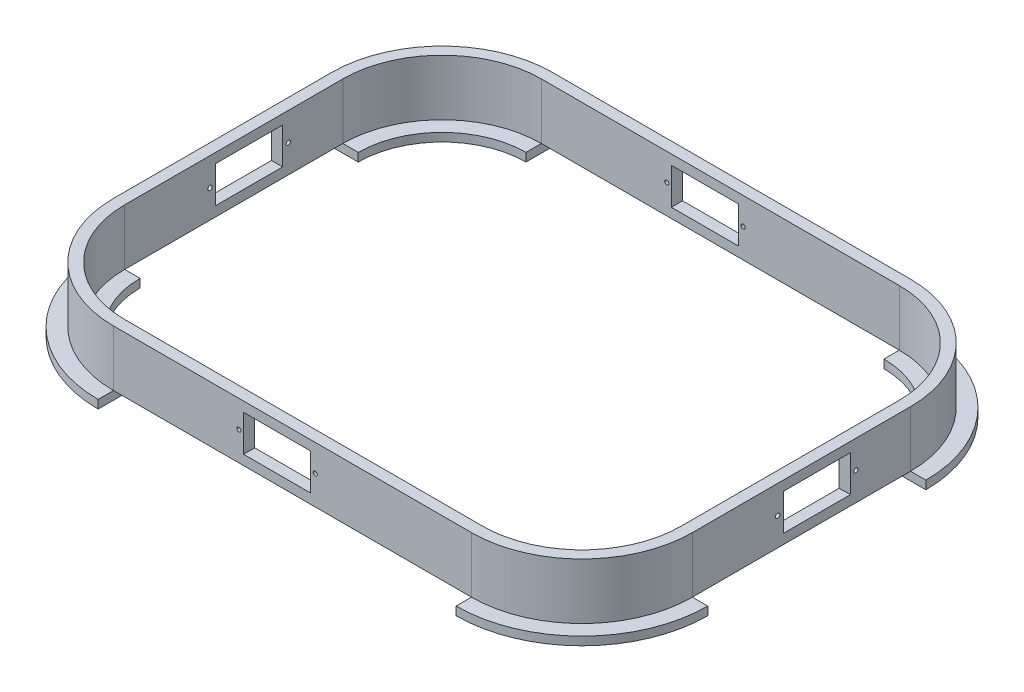
SolidWorks part; units mm, degrees
material "PVC Rigid"
ref_plane "Front Plane" through (0, 0, 0) normal (0, 0, 1) x (1, 0, 0)
ref_plane "Top Plane" through (0, 0, 0) normal (0, 1, 0) x (1, 0, 0)
ref_plane "Right Plane" through (0, 0, 0) normal (1, 0, 0) x (0, 0, -1)
sketch "Sketch1" plane through (0, 0, 0) normal (0, 1, 0) x (1, 0, 0)
  line L0 (-64, 84) -> (64, 84)
  line L1 (-64, -69) -> (64, -69)
  line L2 (-94, -39) -> (-94, 39)
  line L3 (-64, 69) -> (64, 69)
  line L4 (94, -39) -> (94, 39)
  line L5 (-94, -69) -> (94, 69) construction
  line L6 (-94, 69) -> (94, -69) construction
  line L7 (109, -39) -> (109, 39)
  line L8 (-64, -84) -> (64, -84)
  line L9 (-109, -39) -> (-109, 39)
  line L10 (-64, 76.5) -> (64, 76.5) construction
  line L11 (101.5, -39) -> (101.5, 39) construction
  line L12 (-64, -76.5) -> (64, -76.5) construction
  line L13 (-101.5, -39) -> (-101.5, 39) construction
  line L14 (-64, 74.5) -> (64, 74.5)
  line L15 (99.5, -39) -> (99.5, 39)
  line L16 (-64, -74.5) -> (64, -74.5)
  line L17 (-99.5, -39) -> (-99.5, 39)
  line L18 (-64, 78.5) -> (64, 78.5)
  line L19 (103.5, -39) -> (103.5, 39)
  line L20 (-64, -78.5) -> (64, -78.5)
  line L21 (-103.5, -39) -> (-103.5, 39)
  line L22 (-64, 80.5) -> (64, 80.5)
  line L23 (105.5, -39) -> (105.5, 39)
  line L24 (-64, -80.5) -> (64, -80.5)
  line L25 (-105.5, -39) -> (-105.5, 39)
  line L26 (-64, 72.5) -> (64, 72.5)
  line L27 (97.5, -39) -> (97.5, 39)
  line L28 (-64, -72.5) -> (64, -72.5)
  line L29 (-97.5, -39) -> (-97.5, 39)
  line L31 (-64, -189.9551) -> (64, -189.9551)
  line L32 (-64, -189.9551) -> (-64, 189.9551)
  line L33 (-64, 189.9551) -> (64, 189.9551)
  line L34 (64, -189.9551) -> (64, 189.9551)
  line L35 (-64, -189.9551) -> (64, 189.9551) construction
  line L36 (-64, 189.9551) -> (64, -189.9551) construction
  line L37 (-310.5434, -39) -> (310.5434, -39)
  line L38 (-310.5434, -39) -> (-310.5434, 39)
  line L39 (-310.5434, 39) -> (310.5434, 39)
  line L40 (310.5434, -39) -> (310.5434, 39)
  line L41 (-310.5434, -39) -> (310.5434, 39) construction
  line L42 (-310.5434, 39) -> (310.5434, -39) construction
  arc A0 (64, -69) -> (94, -39) centre (64, -39) ccw
  arc A1 (-64, -69) -> (-94, -39) centre (-64, -39) cw
  arc A2 (64, 69) -> (94, 39) centre (64, 39) cw
  arc A3 (-94, 39) -> (-64, 69) centre (-64, 39) cw
  arc A4 (64, 84) -> (109, 39) centre (64, 39) cw
  arc A5 (64, -84) -> (109, -39) centre (64, -39) ccw
  arc A6 (-64, -84) -> (-109, -39) centre (-64, -39) cw
  arc A7 (-109, 39) -> (-64, 84) centre (-64, 39) cw
  arc A8 (64, 76.5) -> (101.5, 39) centre (64, 39) cw construction
  arc A9 (64, -76.5) -> (101.5, -39) centre (64, -39) ccw construction
  arc A10 (-64, -76.5) -> (-101.5, -39) centre (-64, -39) cw construction
  arc A11 (-101.5, 39) -> (-64, 76.5) centre (-64, 39) cw construction
  arc A12 (64, 74.5) -> (99.5, 39) centre (64, 39) cw
  arc A13 (64, -74.5) -> (99.5, -39) centre (64, -39) ccw
  arc A14 (-64, -74.5) -> (-99.5, -39) centre (-64, -39) cw
  arc A15 (-99.5, 39) -> (-64, 74.5) centre (-64, 39) cw
  arc A16 (64, 78.5) -> (103.5, 39) centre (64, 39) cw
  arc A17 (64, -78.5) -> (103.5, -39) centre (64, -39) ccw
  arc A18 (-64, -78.5) -> (-103.5, -39) centre (-64, -39) cw
  arc A19 (-103.5, 39) -> (-64, 78.5) centre (-64, 39) cw
  arc A20 (64, 80.5) -> (105.5, 39) centre (64, 39) cw
  arc A21 (64, -80.5) -> (105.5, -39) centre (64, -39) ccw
  arc A22 (-64, -80.5) -> (-105.5, -39) centre (-64, -39) cw
  arc A23 (-105.5, 39) -> (-64, 80.5) centre (-64, 39) cw
  arc A24 (64, 72.5) -> (97.5, 39) centre (64, 39) cw
  arc A25 (64, -72.5) -> (97.5, -39) centre (64, -39) ccw
  arc A26 (-64, -72.5) -> (-97.5, -39) centre (-64, -39) cw
  arc A27 (-97.5, 39) -> (-64, 72.5) centre (-64, 39) cw
  point P0 (0, 0)
  point P90 (0, 0)
  point P95 (0, 0)
  dimension "D3" = 30
  dimension "D1" = 188
  dimension "D2" = 138
  dimension "D10" = 78
  dimension "D11" = 128
  dimension "D4" = 15
  dimension "D5" = 7.5
  dimension "D8" = 2
  dimension "D9" = 2
extrude "Boss-Extrude1" add sketch "Sketch1" against normal blind 3 contours L24 A22 L25 L37 L9 A6 L8 L32 | A22 L24 L32 L20 A18 L21 L37 L25 | A18 L20 L32 L16 A14 L17 L37 L21 | L28 A26 L29 L37 L17 A14 L16 L32 | A26 L28 L32 L1 A1 L2 L37 L29 | A27 L29 L39 L2 A3 L3 L32 L26 | L29 A27 L26 L32 L14 A15 L17 L39 | A19 L21 L39 L17 A15 L14 L32 L18 | A23 L25 L39 L21 A19 L18 L32 L22 | L25 A23 L22 L32 L0 A7 L9 L39 | A24 L26 L34 L3 A2 L4 L39 L27 | L26 A24 L27 L39 L15 A12 L14 L34 | A16 L18 L34 L14 A12 L15 L39 L19 | A20 L22 L34 L18 A16 L19 L39 L23 | L22 A20 L23 L39 L7 A4 L0 L34 | L28 A25 L27 L37 L4 A0 L1 L34 | A25 L28 L34 L16 A13 L15 L37 L27 | L20 A17 L19 L37 L15 A13 L16 L34 | L24 A21 L23 L37 L19 A17 L20 L34 | A21 L24 L34 L8 A5 L7 L37 L23 region at (-64.6364, 0, -82.25) region at (95.3698, 0, -70.3698) region at (-64.5869, 0, -79.5) region at (92.9299, 0, -67.9299) region at (-64.5586, 0, -76.5) region at (-107.25, 0, 39.6364) region at (91.5357, 0, -66.5357) region at (95.3698, 0, 70.3698) region at (-64.502, 0, -73.5) region at (-104.5, 0, 39.5869) region at (88.7473, 0, -63.7473) region at (92.9299, 0, 67.9299) region at (-64.4738, 0, -70.75) region at (-101.5, 0, 39.5586) region at (87.3531, 0, -62.3531) region at (91.5357, 0, 66.5357) region at (-98.5, 0, 39.502) region at (88.7473, 0, 63.7473) region at (-95.75, 0, 39.4738) region at (87.3531, 0, 62.3531)
extrude "Boss-Extrude2" add sketch "Sketch1<6>" along normal blind 20 contours A19 L21 L39 L17 A15 L14 L32 L18 | L39 L21 L37 L17 | A18 L20 L32 L16 A14 L17 L37 L21 | L20 L34 L16 L32 | L20 A17 L19 L37 L15 A13 L16 L34 | L39 L15 L37 L19 | A16 L18 L34 L14 A12 L15 L39 L19 | L14 L34 L18 L32 region at (0, 0, -76.5) region at (-64.5586, 0, -76.5) region at (91.5357, 0, -66.5357) region at (-101.5, 0, 0) region at (101.5, 0, 0) region at (-101.5, 0, 39.5586) region at (91.5357, 0, 66.5357) region at (0, 0, 76.5)
sketch "Sketch1<6>" plane through (0, 0, 0) normal (0, 1, 0) x (1, 0, 0) same geometry as "Sketch1"
sketch "Sketch3" plane through (-103.5, 0, 0) normal (-1, 0, 0) x (0, 0, 1)
  line L0 (-39, 20) -> (39, 0) construction
  line L1 (39, 0) -> (39, 20)
  line L2 (39, 20) -> (-39, 0) construction
  line L3 (-39, 20) -> (-39, 0) construction
  line L5 (-17.5, 16.5) -> (6.5, 16.5)
  line L6 (-17, 4) -> (6, 4) construction
  line L7 (-17, 4) -> (-17, 16) construction
  line L8 (-17, 16) -> (6, 16) construction
  line L9 (6, 4) -> (6, 16) construction
  line L10 (-17, 4) -> (6, 16) construction
  line L11 (-17, 16) -> (6, 4) construction
  line L12 (6.5, 3.5) -> (6.5, 16.5)
  line L13 (-17.5, 3.5) -> (6.5, 3.5)
  line L14 (-17.5, 3.5) -> (-17.5, 16.5)
  line L15 (-19.5, 18.5) -> (8.5, 18.5) construction
  line L16 (8.5, 1.5) -> (8.5, 18.5) construction
  line L17 (-19.5, 1.5) -> (8.5, 1.5) construction
  line L18 (-19.5, 1.5) -> (-19.5, 18.5) construction
  circle A0 centre (0, 10) radius 6
  circle A1 centre (8.5, 10) radius 0.8
  circle A2 centre (-19.5, 10) radius 0.75
  point P11 (-1.4445, 9.4895)
  dimension "D4" = 12
  dimension "D6" = 1.5
  dimension "D7" = 1.6
  dimension "D1" = 23
  dimension "D2" = 12
extrude "Cut-Extrude1" cut sketch "Sketch3" against normal up to surface (207 mm away) contours L14 L13 L12 L5 A0 | A2 | A0 | A1 | A1 region at (-103.5, 10, -8.6273) region at (-103.5, 10, 0) region at (-103.5, 10, 8.5) region at (-103.5, 10, -19.5) up to face at (103.5, 10, 0)
sketch "Sketch4" plane through (0, 0, 78.5) normal (0, 0, 1) x (1, 0, 0)
  line L0 (-64, 20) -> (64, 0) construction
  line L1 (64, 0) -> (64, 20)
  line L2 (64, 20) -> (-64, 0) construction
  line L3 (-17.5, 16.5) -> (6.5, 16.5)
  line L4 (-17, 4) -> (6, 4) construction
  line L5 (-17, 4) -> (-17, 16) construction
  line L6 (-17, 16) -> (6, 16) construction
  line L7 (6, 4) -> (6, 16) construction
  line L8 (-17, 4) -> (6, 16) construction
  line L9 (-17, 16) -> (6, 4) construction
  line L10 (6.5, 3.5) -> (6.5, 16.5)
  line L11 (-17.5, 3.5) -> (6.5, 3.5)
  line L12 (-17.5, 3.5) -> (-17.5, 16.5)
  line L13 (-19.15, 18.5) -> (8.15, 18.5) construction
  line L14 (8.15, 2.2) -> (8.15, 18.5) construction
  line L15 (-19.15, 2.2) -> (8.15, 2.2) construction
  line L16 (-19.15, 2.2) -> (-19.15, 18.5) construction
  circle A0 centre (0, 10) radius 6
  circle A1 centre (8.15, 10.35) radius 0.75
  circle A2 centre (-19.15, 10.35) radius 0.75
  point P6 (-6.5077, 1.9014)
  point P29 (0, 10)
  dimension "D7" = 2
  dimension "D1" = 23
  dimension "D2" = 12
  dimension "D3" = 12
  dimension "D4" = 1.5
  dimension "D5" = 1.5
  dimension "D6" = 0.5
extrude "Cut-Extrude3" cut sketch "Sketch4" against normal up to surface (157 mm away) contours L12 L11 L10 L3 A0 | A2 | A1 | A0 region at (-8.6273, 10, 78.5) region at (0, 10, 78.5) region at (8.15, 10.35, 78.5) region at (-19.15, 10.35, 78.5) up to face at (0, 10, -78.5)
equation "\"Food_Width\" = 120"
equation "\"D1@Sketch1\"=\"Food_Length\"+\"Allowance\""
equation "\"Food_Length\" = 170"
equation "\"Allowance\"= 18"
equation "\"Inner Fillet\"= 30"
equation "\"D2@Sketch1\"=\"Food_Width\"+\"Allowance\""
equation "\"Frame_Width\"= 15"
equation "\"D4@Sketch1\"=\"Frame_Width\""
equation "\"D5@Sketch1\"=\"D4@Sketch1\"/2"
equation "\"CAM Thickness\"= 3"
equation "\"CAM Allowance\"= 0.5"
equation "\"D6@Sketch1\"=\"CAM Thickness\"/2+\"CAM Allowance\""
equation "\"D7@Sketch1\"=\"D6@Sketch1\""
equation "\"Wall_Thickness\"= 2"
equation "\"Base_Thickness\"= 3"
equation "\"D8@Sketch1\"=\"Wall_Thickness\""
equation "\"D9@Sketch1\"=\"Wall_Thickness\""
equation "\"Wall_Height\"= 20"
equation "\"D1@Boss-Extrude1\"=\"Base_Thickness\""
equation "\"D1@Boss-Extrude2\"=\"Wall_Height\""
equation "\"Shaft_Diam\"= 6"
equation "\"Shaft_Tolerance\"= 1"
equation "\"Corner_Allowance\"=30"
equation "\"D10@Sketch1\"=\"D2@Sketch1\"-\"Corner_Allowance\"*2"
equation "\"D11@Sketch1\"=\"D1@Sketch1\"-\"Corner_Allowance\"*2"
equation "\"Servo_Length\"= 23"
equation "\"D1@Sketch3\"=\"Servo_Length\""
equation "\"Servo_Width\"= 12"
equation "\"D2@Sketch3\"=\"Servo_Width\""
equation "\"D1@Sketch4\"=\"Servo_Length\""
equation "\"D2@Sketch4\"=\"Servo_Width\""
equation "\"D3@Sketch1\"=\"Inner Fillet\""
